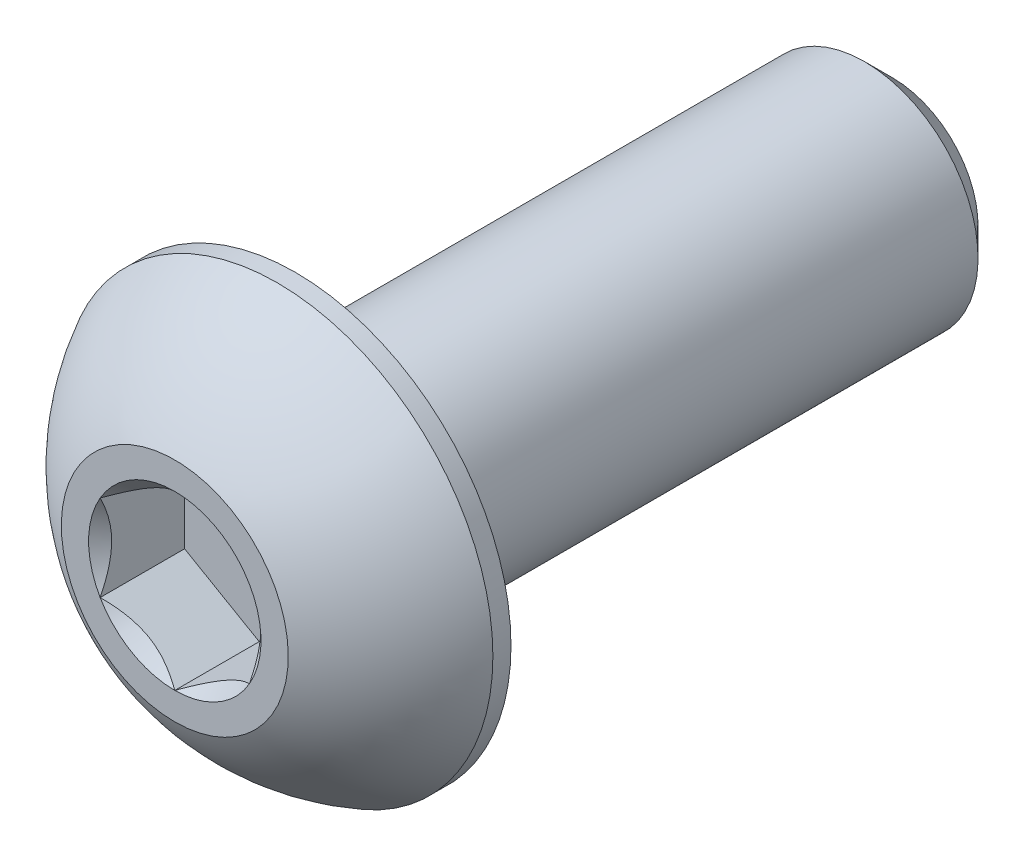
SolidWorks part; units mm, degrees
ref_plane "Front" through (0, 0, 0) normal (0, 0, 1) x (1, 0, 0)
ref_plane "Top" through (0, 0, 0) normal (0, 1, 0) x (1, 0, 0)
ref_plane "Right" through (0, 0, 0) normal (1, 0, 0) x (0, 0, -1)
sketch "Sketch1" plane through (0, 0, 0) normal (1, 0, 0) x (0, 0, -1)
  line L2 (2.5654, 2.413) -> (15.2654, 2.413)
  line L3 (15.2654, 2.413) -> (15.2654, 0)
  line L4 (15.2654, 0) -> (2.5654, 0)
  line L6 (2.1806, 4.5847) -> (2.5654, 4.5847) construction
  line L7 (15.2654, 2.413) -> (15.2654, -2.413) construction
  line L8 (0, 0) -> (2.5654, 0) construction
  line L9 (2.5654, 4.5847) -> (2.5654, -4.5847) construction
  line L11 (2.5654, 2.413) -> (2.5654, 0)
  line L13 (0, 1.5875) -> (0, -1.5875) construction
  line L14 (0, 1.5875) -> (0, 2.413) construction
  arc A3 (0, 2.413) -> (2.1806, 4.5847) centre (4.5749, 0) cw construction
  dimension "D1" = 0.3848
revolve "Revolve1" add sketch "Sketch1" angle 360 mid plane about L4
sketch "Sketch3" plane through (0, 0, -15.2654) normal (0, 0, -1) x (-1, 0, 0)
  circle A0 centre (0, 0) radius 2.413
curve "Helix/Spiral1" pitch 0.7937 height 13.4937 turns 17
sketch "Sketch2" plane through (0, 0, 0) normal (1, 0, 0) x (0, 0, -1)
  line L0 (15.2654, 2.413) -> (15.9599, 2.413)
  line L1 (15.9599, 2.413) -> (15.6623, 1.8974)
  line L2 (15.6623, 1.8974) -> (15.5631, 1.8974)
  line L3 (15.5631, 1.8974) -> (15.2654, 2.413)
  line L4 (15.4142, 2.1552) -> (15.8111, 2.1552) construction
  dimension "D1" = 60
  dimension "D2" = 0.0992
  dimension "D3" = 0.3969
chamfer "Chamfer1" distance 0.5953 angle 45 1 edges at (0, 2.413, -15.2654)
sweep "Cut-Sweep1" [suppressed] cut profiles "Sketch2" path "Helix/Spiral1"
sketch "Sketch7" plane through (0, 0, 0) normal (1, 0, 0) x (0, 0, -1)
  line L6 (2.1806, 4.5847) -> (2.5654, 4.5847) construction
  line L8 (0, 0) -> (2.5654, 0) construction
  line L11 (2.5654, 4.5847) -> (2.5654, -4.5847) construction
  line L12 (2.1806, 4.5847) -> (2.5654, 4.5847)
  line L13 (0, 0) -> (2.5654, 0)
  line L14 (0, 1.5875) -> (0, -1.5875) construction
  line L15 (2.5654, 4.5847) -> (2.5654, 0)
  line L16 (0, 2.413) -> (0, 0)
  arc A2 (2.1806, 4.5847) -> (0, 2.413) centre (4.5749, 0) ccw construction
  arc A3 (2.1806, 4.5847) -> (0, 2.413) centre (4.5749, 0) ccw
revolve "Revolve2" add sketch "Sketch7" angle 360 mid plane about L13
sketch "Sketch5" plane through (0, 0, 0) normal (0, 0, 1) x (1, 0, 0)
  line L1 (1.5875, -0.9165) -> (1.5875, 0.9165)
  line L2 (1.5875, 0.9165) -> (0, 1.8331)
  line L3 (0, 1.8331) -> (-1.5875, 0.9165)
  line L4 (-1.5875, 0.9165) -> (-1.5875, -0.9165)
  line L5 (-1.5875, -0.9165) -> (0, -1.8331)
  line L6 (0, -1.8331) -> (1.5875, -0.9165)
  circle A0 centre (0, 0) radius 1.5875 construction
extrude "Cut-Extrude2" cut sketch "Sketch5" against normal blind 1.7958
sketch "Sketch6" plane through (0, 0, 0) normal (0, 0, 1) x (1, 0, 0)
  circle A0 centre (0, 0) radius 1.8331
extrude "Cut-Extrude3" cut sketch "Sketch6" against normal blind 1.7958 draft 45
sketch "Sketch9" [suppressed] plane through (0, 0, -2.5654) normal (0, 0, 1) x (1, 0, 0)
  circle A2 centre (0, 0) radius 2.413
extrude "Boss-Extrude2" [suppressed] add sketch "Sketch9" against normal offset from surface (9.525 mm away) 31.75
sketch "Sketch10" plane through (0, 0, 0) normal (1, 0, 0) x (0, 0, -1)
  line L0 (15.2654, 2.413) -> (15.2654, -2.413) construction
  point P0 (14.0748, -2.413)
  dimension "D1" = 1.1906
equation "\"D3@Helix/Spiral1\" = \"Lg@Sketch1\" + \"D4@Helix/Spiral1\""
equation "\"D2@Sketch2\" = \"D4@Helix/Spiral1\" * .125"
equation "\"D3@Sketch2\" = \"D4@Helix/Spiral1\" * .5"
equation "\"D1@Chamfer1\" = \"D4@Helix/Spiral1\" * .75"
equation "\"D1@Cut-Extrude2\" = \"Head Ht@Sketch1\" * .7"
equation "\"D1@Sketch1\" = \"Head Ht@Sketch1\" * .15"
equation "\"D1@Sketch10\" = \"D4@Helix/Spiral1\" * 1.5"
equation "\"D1@Cut-Extrude3\" = \"D1@Cut-Extrude2\""
